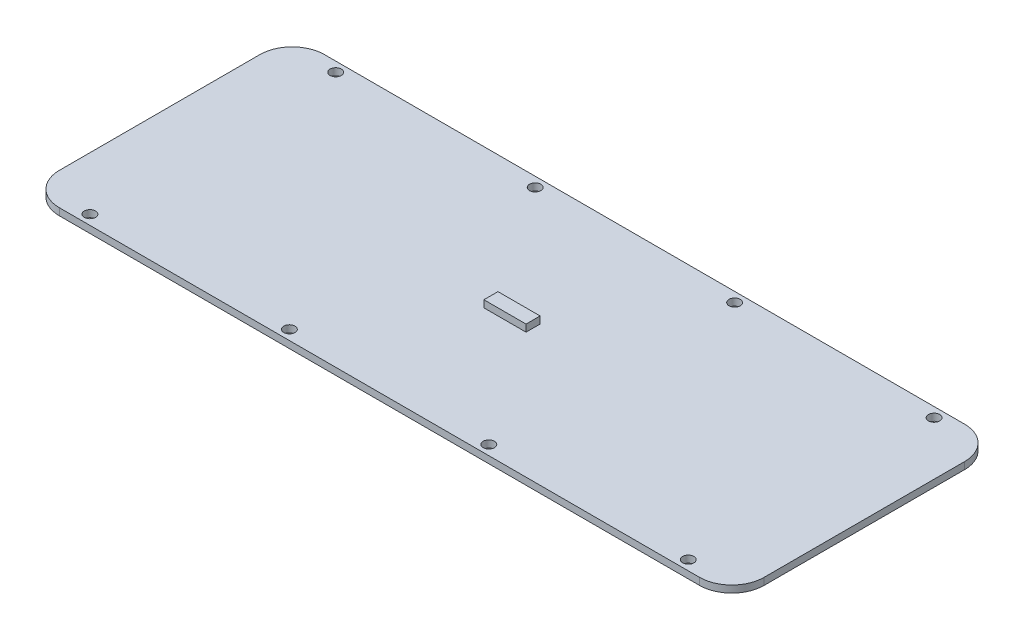
SolidWorks part; units mm, degrees
ref_plane "Front Plane" through (0, 0, 0) normal (0, 0, 1) x (1, 0, 0)
ref_plane "Top Plane" through (0, 0, 0) normal (0, 1, 0) x (1, 0, 0)
ref_plane "Right Plane" through (0, 0, 0) normal (1, 0, 0) x (0, 0, -1)
sketch "Sketch2" plane through (0, 0, 0) normal (0, 1, 0) x (1, 0, 0)
  line L0 (0, 0) -> (0, 87.5) construction
  line L1 (-227.9, -94.4) -> (227.9, -94.4)
  line L2 (-250.9, -71.4) -> (-250.9, 71.4)
  line L3 (-227.9, 94.4) -> (227.9, 94.4)
  line L4 (250.9, -71.4) -> (250.9, 71.4)
  line L5 (-250.9, -94.4) -> (250.9, 94.4) construction
  line L6 (-250.9, 94.4) -> (250.9, -94.4) construction
  line L7 (-841.7998, 87.5) -> (49158.2002, 87.5) construction
  line L8 (0, 0) -> (-113.8164, 0) construction
  line L10 (-15, -5) -> (15, -5)
  line L11 (-15, -5) -> (-15, 5)
  line L12 (-15, 5) -> (15, 5)
  line L13 (15, -5) -> (15, 5)
  line L14 (-15, -5) -> (15, 5) construction
  line L15 (-15, 5) -> (15, -5) construction
  arc A0 (-227.9, -94.4) -> (-250.9, -71.4) centre (-227.9, -71.4) cw
  arc A1 (227.9, -94.4) -> (250.9, -71.4) centre (227.9, -71.4) ccw
  arc A2 (227.9, 94.4) -> (250.9, 71.4) centre (227.9, 71.4) cw
  arc A3 (-250.9, 71.4) -> (-227.9, 94.4) centre (-227.9, 71.4) cw
  circle A4 centre (-213, 87.5) radius 4
  circle A5 centre (-71, 87.5) radius 4
  circle A6 centre (71, 87.5) radius 4
  circle A7 centre (213, 87.5) radius 4
  circle A8 centre (213, -87.5) radius 4
  circle A9 centre (71, -87.5) radius 4
  circle A10 centre (-71, -87.5) radius 4
  circle A11 centre (-213, -87.5) radius 4
  point P0 (0, 0)
  dimension "D3" = 23
  dimension "D6" = 8
  dimension "D1" = 188.8
  dimension "D2" = 501.8
  dimension "D4" = 6.9
  dimension "D5" = 37.9
  dimension "D7" = 142
  dimension "D8" = 142
  dimension "D9" = 142
  dimension "D10" = 10
  dimension "D11" = 30
extrude "Boss-Extrude1" add sketch "Sketch2" along normal blind 5
extrude "Boss-Extrude2" add sketch "Sketch2<2>" along normal blind 10 contours L10 L13 L12 L11 region at (0, 0, 0)
sketch "Sketch2<2>" plane through (0, 0, 0) normal (0, 1, 0) x (1, 0, 0) same geometry as "Sketch2"
equation "\"D2@Sketch2\"=502-0.2"
equation "\"D1@Sketch2\"=189-0.2"
equation "\"D5@Sketch2\"=38-(0.2/2)"
equation "\"D4@Sketch2\"=7-(0.2/2)"
